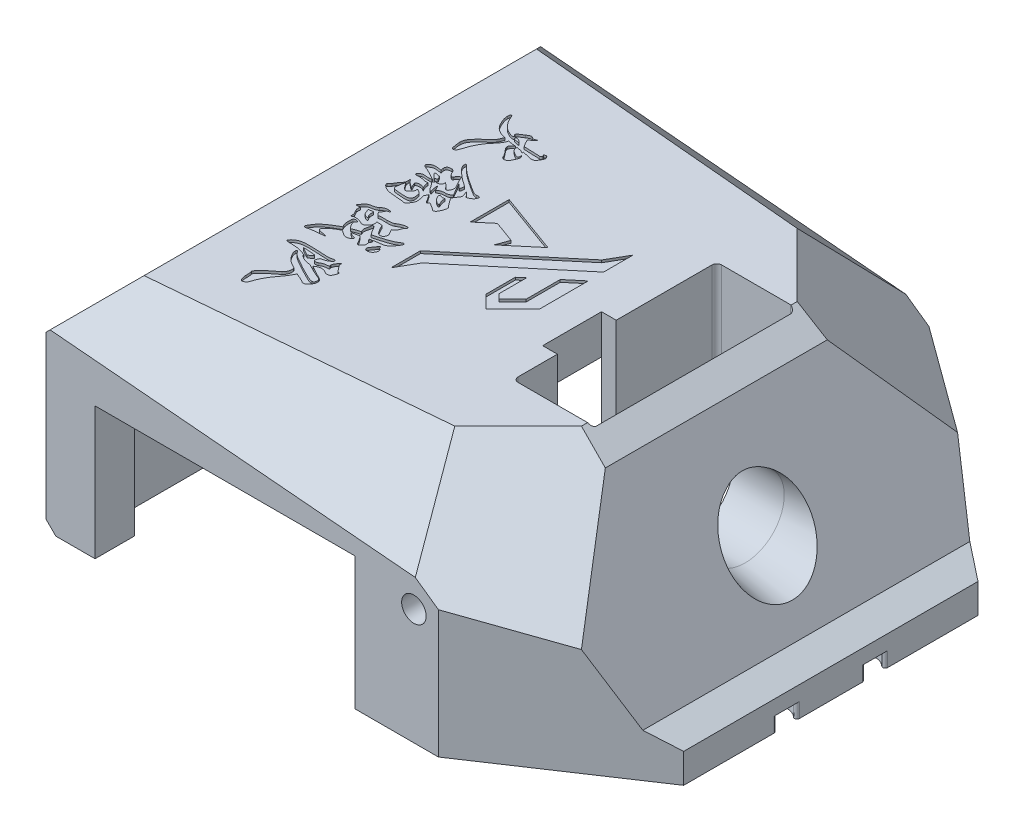
SolidWorks part; units mm, degrees
ref_plane "前视基准面" through (0, 0, 0) normal (0, 0, 1) x (1, 0, 0)
ref_plane "上视基准面" through (0, 0, 0) normal (0, 1, 0) x (1, 0, 0)
ref_plane "右视基准面" through (0, 0, 0) normal (1, 0, 0) x (0, 0, -1)
sketch "草图1" plane through (0, 0, 0) normal (0, 0, 1) x (1, 0, 0)
  line L0 (0, 0) -> (0, 45)
  line L1 (0, 45) -> (84.15, 45)
  line L2 (110, 6) -> (105, 8.8868)
  line L3 (110, 6) -> (110, 0)
  line L4 (110, 0) -> (0, 0)
  line L5 (62, 23.5) -> (92.5, 23.5) construction
  line L6 (105, 8.8868) -> (84.15, 45)
  dimension "D1" = 110
  dimension "D2" = 6
  dimension "D3" = 45
  dimension "D4" = 23.5
  dimension "D5" = 30.5
  dimension "D6" = 62
  dimension "D7" = 60
  dimension "D8" = 60
  dimension "D9" = 5
extrude "凸台-拉伸1" add sketch "草图1" along normal mid plane 100
sketch "草图4" plane through (0, 45, 0) normal (0, 1, 0) x (1, 0, 0)
  line L0 (110, 30) -> (80, 50)
  line L1 (110, -50) -> (110, 50) construction
  line L2 (84.15, 50) -> (0, 50) construction
  line L3 (80, 50) -> (110, 50)
  line L4 (110, 50) -> (110, 30)
  line L5 (110, -50) -> (110, -30)
  line L6 (110, -30) -> (80, -50)
  line L7 (84.15, -50) -> (0, -50) construction
  line L8 (80, -50) -> (110, -50)
  dimension "D1" = 60
  dimension "D2" = 30
extrude "切除-拉伸2" cut sketch "草图4" against normal through all
sketch "草图7" plane through (0, 45, 0) normal (0, 1, 0) x (1, 0, 0)
  line L0 (10, 40) -> (10, -40)
  line L1 (10, -40) -> (68.2459, -34.9041)
  line L2 (68.2459, -34.9041) -> (84.15, -19)
  line L3 (84.15, -47.2333) -> (84.15, 47.2333) construction
  line L4 (84.15, -19) -> (84.15, 19)
  line L5 (84.15, 19) -> (68.2459, 34.9041)
  line L6 (68.2459, 34.9041) -> (10, 40)
  line L7 (0, 0) -> (84.15, 0) construction
  line L9 (0, -50) -> (0, 50) construction
  line L10 (80, 50) -> (0, 50) construction
  dimension "D1" = 80
  dimension "D2" = 10
  dimension "D3" = 5
  dimension "D4" = 90
  dimension "D5" = 38
extrude "切除-拉伸4" cut sketch "草图7" against normal through all draft 45 flip side to cut
sketch "草图6" plane through (0, 0, 0) normal (0, -1, 0) x (1, 0, 0)
  line L0 (5, 37) -> (5, 19)
  line L1 (0, 50) -> (80, 50) construction
  line L2 (5, 19) -> (0, 19)
  line L3 (0, 50) -> (0, -50) construction
  line L4 (0, 19) -> (0, -29)
  line L5 (0, -29) -> (5, -29)
  line L6 (5, -29) -> (5, -50)
  line L7 (0, -50) -> (80, -50) construction
  line L8 (5, -50) -> (65, -50)
  line L9 (65, -50) -> (73, -42)
  line L10 (63, 50) -> (10, 50)
  line L11 (5, 37) -> (10, 42)
  line L12 (10, 42) -> (10, 50)
  line L13 (63, 40.2) -> (85.6861, 40.2)
  line L14 (85.6861, 40.2) -> (95, 33.9907)
  line L15 (95, 33.9907) -> (95, 10)
  line L16 (80, -50) -> (110, -30) construction
  line L17 (63, 40.2) -> (63, 50)
  line L18 (110, 30) -> (80, 50) construction
  line L19 (95, 10) -> (80, 10)
  line L20 (80, 10) -> (80, -10)
  line L21 (80, -10) -> (95, -10)
  line L22 (95, -10) -> (95, -33.9907)
  line L23 (110, 30) -> (110, -30) construction
  line L24 (73, -42) -> (82.9861, -42)
  line L25 (82.9861, -42) -> (95, -33.9907)
  point P27 (80, 0)
  dimension "D1" = 5
  dimension "D2" = 31
  dimension "D3" = 18
  dimension "D4" = 45
  dimension "D5" = 5
  dimension "D6" = 21
  dimension "D7" = 63
  dimension "D8" = 9.8
  dimension "D9" = 5
  dimension "D10" = 15
  dimension "D11" = 5
  dimension "D12" = 20
  dimension "D13" = 30
  dimension "D14" = 60
  dimension "D15" = 45
  dimension "D16" = 8
extrude "切除-拉伸3" cut sketch "草图6" against normal blind 15
ref_plane "基准面1" through (92.5, 23.5, 0) normal (1, 0, 0) x (0, 0, -1)
sketch "草图8" plane through (0, 45, 0) normal (0, 1, 0) x (1, 0, 0)
  line L0 (110, -30) -> (110, 30) construction
  line L1 (66, 20.75) -> (82, 20.75)
  line L2 (66, 20.75) -> (66, 0.25)
  line L3 (66, -20.75) -> (82, -20.75)
  line L4 (82, 20.75) -> (82, -20.75)
  line L5 (66, -11.75) -> (66, -20.75)
  line L6 (66, 0.25) -> (63, 0.25)
  line L8 (66, -11.75) -> (63, -11.75)
  line L9 (63, 0.25) -> (63, -11.75)
  point P4 (82, 0)
  dimension "D1" = 16
  dimension "D2" = 41.5
  dimension "D3" = 28
  dimension "D4" = 3
  dimension "D5" = 12
  dimension "D6" = 9
extrude "切除-拉伸5" cut sketch "草图8" against normal through all
fillet "圆角1" radius 1 4 edges at (66, 30, 20.75) (82, 30, 20.75) (82, 30, -20.75) (66, 30, -20.75)
sketch "草图2" plane through (92.5, 23.5, 0) normal (1, 0, 0) x (0, 0, -1)
  line L0 (0, -14.6132) -> (0, 21.5) construction
  circle A0 centre (0, 0) radius 8
  dimension "D1" = 16
extrude "切除-拉伸1" cut sketch "草图2" along normal through all draft 10 and the other way up to next (10.5 mm away) draft outward yes
sketch "草图9" plane through (0, 0, 0) normal (0, 0, 1) x (1, 0, 0)
  line L0 (82, 45) -> (82, 15) construction
  line L1 (63, 0) -> (80, 0) construction
  circle A0 centre (75, 23.6) radius 1.1
  dimension "D1" = 2.2
  dimension "D3" = 23.6
  dimension "D2" = 7
extrude "切除-拉伸6" cut sketch "草图9" against normal through all both and the other way through all
sketch "草图10" plane through (0, 0, 50) normal (0, 0, 1) x (1, 0, 0)
  circle A0 centre (75, 23.6) radius 2.5
  dimension "D1" = 5
extrude "切除-拉伸7" cut sketch "草图10" against normal blind 24
sketch "草图11" plane through (0, 0, -50) normal (0, 0, -1) x (-1, 0, 0)
  circle A0 centre (-75, 23.6) radius 2.5
  dimension "D1" = 5
extrude "切除-拉伸8" cut sketch "草图11" against normal blind 24
sketch "草图12" plane through (0, 15, 0) normal (0, -1, 0) x (1, 0, 0)
  line L0 (63, 50) -> (63, -50)
  line L1 (0, 19) -> (0, -29) construction
  line L2 (5, 12) -> (0, 12)
  line L3 (63, 40.2) -> (63, 50) construction
  line L4 (5, -8) -> (0, -8)
  line L5 (0, 12) -> (0, -8)
  line L6 (5, -8) -> (5, -29)
  line L28 (82, -10) -> (82, -19.75)
  line L29 (81, -20.75) -> (67, -20.75)
  line L30 (66, -19.75) -> (66, -0.25)
  line L31 (66, -0.25) -> (63, -0.25)
  line L32 (63, -0.25) -> (63, 11.75)
  line L33 (63, 11.75) -> (66, 11.75)
  line L34 (66, 11.75) -> (66, 19.75)
  line L35 (67, 20.75) -> (81, 20.75)
  line L36 (82, 19.75) -> (82, 10)
  line L37 (82, 10) -> (95, 10)
  line L38 (95, 10) -> (95, 33.9907)
  line L39 (95, 33.9907) -> (85.6861, 40.2)
  line L40 (85.6861, 40.2) -> (63, 40.2)
  line L41 (63, 40.2) -> (63, 50)
  line L42 (63, 50) -> (10, 50)
  line L43 (10, 50) -> (10, 42)
  line L44 (10, 42) -> (5, 37)
  line L45 (5, 37) -> (5, 19)
  line L46 (5, 19) -> (0, 19)
  line L47 (0, 19) -> (0, -29)
  line L48 (0, -29) -> (5, -29)
  line L49 (5, -29) -> (5, -50)
  line L50 (5, -50) -> (65, -50)
  line L51 (65, -50) -> (73, -42)
  line L52 (73, -42) -> (82.9861, -42)
  line L53 (82.9861, -42) -> (95, -33.9907)
  line L54 (95, -33.9907) -> (95, -10)
  line L55 (95, -10) -> (82, -10)
  line L70 (63, 50) -> (10, 50)
  line L71 (10, 50) -> (10, 42)
  line L72 (10, 42) -> (5, 37)
  line L73 (5, 37) -> (5, 12)
  line L77 (5, -29) -> (5, -50)
  line L78 (5, -50) -> (63, -50)
  arc A4 (81, -20.75) -> (82, -19.75) centre (81, -19.75) ccw
  arc A5 (66, -19.75) -> (67, -20.75) centre (67, -19.75) ccw
  arc A6 (67, 20.75) -> (66, 19.75) centre (67, 19.75) ccw
  arc A7 (82, 19.75) -> (81, 20.75) centre (81, 19.75) ccw
  dimension "D3" = 20
  dimension "D4" = 8
  dimension "D1" = 0
extrude "切除-拉伸9" cut sketch "草图12" against normal blind 12
sketch "草图13" plane through (0, 27, 0) normal (0, -1, 0) x (1, 0, 0)
  line L0 (63, -50) -> (63, -0.25) construction
  line L1 (5, 37) -> (63, 37)
  line L2 (5, 37) -> (5, 12)
  line L3 (5, -35) -> (63, -35)
  line L4 (63, 37) -> (63, -35)
  line L5 (5, -50) -> (63, -50) construction
  line L6 (0, -8) -> (5, -8) construction
  line L7 (0, 12) -> (0, -8) construction
  line L8 (5, 12) -> (0, 12) construction
  line L9 (0, -8) -> (5, -8)
  line L10 (0, 12) -> (0, -8)
  line L11 (5, 12) -> (0, 12)
  line L12 (5, -8) -> (5, -35)
  dimension "D1" = 15
extrude "切除-拉伸10" cut sketch "草图13" against normal blind 10
fillet "圆角2" radius 5 2 edges at (95, 7.5, -10) (95, 7.5, 10)
fillet "圆角3" radius 2 7 edges at (64.5, 15, 11.75) (64.5, 15, -0.25) (2.5, 15, -29) (2.5, 15, 19) (2.5, 15, 12) (2.5, 15, -8) (63, 7.5, 40.2)
sketch "草图14" plane through (0, 0, 0) normal (0, -1, 0) x (1, 0, 0)
  line L0 (0, 0) -> (110, 0) construction
  line L1 (110, 30) -> (110, -30) construction
  circle A0 centre (106, 25) radius 1.35
  circle A1 centre (106, -25) radius 1.35
  dimension "D1" = 50
  dimension "D2" = 4
  dimension "D3" = 2.7
extrude "切除-拉伸11" cut sketch "草图14" against normal blind 5
sketch "草图15" plane through (0, 0, 0) normal (0, -1, 0) x (1, 0, 0)
  line L0 (0, 0) -> (110, 0) construction
  line L1 (110, 30) -> (110, -30) construction
  circle A0 centre (107, 9) radius 3.1
  circle A1 centre (107, -9) radius 3.1
  circle A2 centre (96, 9) radius 3.1
  circle A3 centre (96, -9) radius 3.1
  dimension "D1" = 18
  dimension "D2" = 6.2
  dimension "D3" = 14
  dimension "D4" = 3
extrude "切除-拉伸12" cut sketch "草图15" against normal blind 3
fillet "圆角4" radius 0.5 4 edges at (110, 1.5, -9.781) (110, 1.5, -8.219) (110, 1.5, 8.219) (110, 1.5, 9.781)
sketch "草图16" plane through (0, 45, 0) normal (0, 1, 0) x (1, 0, 0)
  line L0 (20, 28) -> (20, -22) construction
  line L1 (10, 40) -> (10, -40) construction
  line L2 (0, -12) -> (0, -50) construction
  text T0 "火锅战队" font "华文行楷" height 10
  point P8 (20, 3)
  point P10 (45, 0)
  line B0 (53.1067, -5.2078) -> (50.3074, -8.0072)
  line B1 (49.3742, -1.405) -> (48.1301, -2.449)
  line B2 (53.1067, 1.7269) -> (53.1067, -5.2078)
  line B3 (49.3742, -7.074) -> (49.3742, -1.405)
  line B4 (46.2245, 6.1029) -> (33.7829, 10.6313)
  line B5 (48.1301, -2.449) -> (48.1301, -8.4691)
  line B6 (56.2171, -5.6164) -> (56.2171, 4.3369)
  line B7 (33.7829, 10.6313) -> (33.7829, 2.6997)
  line B8 (48.1301, -8.4691) -> (50.7472, -11.0863)
  line B9 (50.7472, -11.0863) -> (56.2171, -5.6164)
  line B10 (40.2677, 1.1046) -> (46.2245, 6.1029)
  line B11 (41.188, 3.633) -> (40.2677, 1.1046)
  line B12 (50.3074, -8.0072) -> (49.3742, -7.074)
  line B13 (36.7989, 5.2305) -> (41.188, 3.633)
  line B14 (33.7829, 2.6997) -> (36.7989, 5.2305)
  line B15 (56.2171, 4.3369) -> (53.1067, 1.7269)
  line B16 (56.2171, 13.4542) -> (56.2171, 7.4542)
  line B17 (56.2171, 7.4542) -> (36.1165, -9.4123)
  line B18 (36.1165, -9.4123) -> (33.7829, -13.4542)
  line B19 (33.7829, -13.4542) -> (33.7829, -7.4542)
  line B20 (33.7829, -7.4542) -> (53.8835, 9.4123)
  line B21 (53.8835, 9.4123) -> (56.2171, 13.4542)
  dimension "D1" = 10
  dimension "D2" = 50
  dimension "D3" = 3
  dimension "D4" = 45
sketch_block_instance "块5-1"
sketch_block "块5" parameters "D1"=5, "D2"=30, "D3"=10
sketch_block_instance "块4-1"
sketch_block "块4"
extrude "切除-拉伸13" cut sketch "草图16" against normal blind 0.5
sketch "草图17" plane through (0, 0, 0) normal (-1, 0, 0) x (0, 0, 1)
  line L0 (50, 0) -> (19, 0) construction
  line L1 (50, 35) -> (50, 0) construction
  line L2 (-50, 35) -> (-50, 0) construction
  circle A0 centre (23, 6) radius 1.6
  circle A1 centre (-33, 6) radius 1.6
  dimension "D1" = 6
  dimension "D2" = 27
  dimension "D3" = 3.2
  dimension "D4" = 17
extrude "切除-拉伸14" cut sketch "草图17" against normal up to next
chamfer "倒角5" distance 2 angle 45 2 edges at (0, 0, -39.5) (0, 0, 34.5)
chamfer "倒角6" distance 5 distance2 3 1 edges at (84.15, 45, 0) first distance on face at (95.5473, 25.2594, 0)
sketch "草图18" [suppressed] plane through (0, 0, 0) normal (0, -1, 0) x (1, 0, 0)
  line L0 (82, 10) -> (82, 19.75) construction
  line L1 (82, -15.1) -> (110, -15.1)
  line L2 (82, -15.1) -> (82, 15.1)
  line L3 (82, 15.1) -> (110, 15.1)
  line L4 (110, -15.1) -> (110, 15.1)
  line L5 (110, -11.5904) -> (110, -30) construction
  line L6 (82, 10) -> (82, -10) construction
  point P11 (82, 0)
  point P12 (82, 0)
  dimension "D1" = 30.2
extrude "切除-拉伸15" [suppressed] cut sketch "草图18" against normal through all
sketch "草图19" [suppressed] plane through (0, 0, 0) normal (0, 0, 1) x (1, 0, 0)
  line L0 (110, 0) -> (80, 0) construction
  line L1 (110, 0) -> (110, 6) construction
  circle A0 centre (100, 8) radius 1.6
  dimension "D1" = 3.2
  dimension "D2" = 8
  dimension "D3" = 10
extrude "切除-拉伸16" [suppressed] cut sketch "草图19" against normal through all both and the other way through all
ref_plane "基准面2" [suppressed] through (0, 0, 20.1) normal (0, 0, -1) x (-1, 0, 0)
sketch "草图20" [suppressed] plane through (0, 0, 20.1) normal (0, 0, -1) x (-1, 0, 0)
  circle A0 centre (-100, 8) radius 3
  dimension "D1" = 6
extrude "切除-拉伸20" [suppressed] cut sketch "草图20" against normal through all
mirror "镜向1" [suppressed] about plane through (0, 0, 0) normal (0, 0, 1)
sketch "草图21" plane through (0, 0, 0) normal (0, -1, 0) x (1, 0, 0)
  line L0 (110, 30) -> (110, 11.5904) construction
  line L1 (110, 15) -> (82, 15)
  line L2 (110, 15) -> (110, -15)
  line L3 (110, -15) -> (82, -15)
  line L4 (82, 15) -> (82, -15)
  line L5 (82, -19.75) -> (82, -10) construction
  line L6 (110, 6.4096) -> (110, -6.4096) construction
  point P9 (110, 0)
  point P12 (110, 0)
  dimension "D1" = 30
extrude "切除-拉伸21" [suppressed] cut sketch "草图21" against normal through all flip side to cut
sketch "草图22" [suppressed] plane through (0, 0, 15) normal (0, 0, 1) x (1, 0, 0)
  line L0 (110, 6) -> (110, 0) construction
  line L1 (110, 0) -> (95, 0) construction
  circle A0 centre (100, 8) radius 1.35
  point P6 (102.5, 0)
  dimension "D1" = 10
  dimension "D2" = 8
  dimension "D3" = 2.7
extrude "切除-拉伸22" [suppressed] cut sketch "草图22" against normal through all
